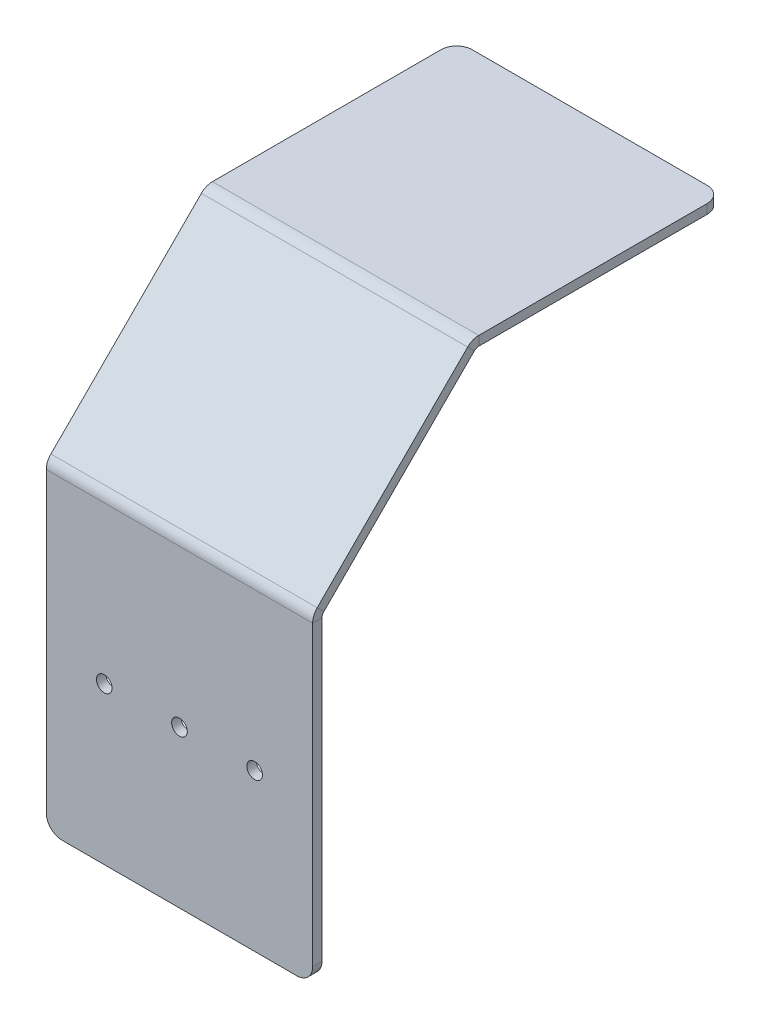
SolidWorks part; units mm, degrees
note: The reader was unsure of these and kept them because the rebuilt part matched: flange length of "Brida de arista1", "Brida de arista2".
ref_plane "Alzado" through (0, 0, 0) normal (0, 0, 1) x (1, 0, 0)
ref_plane "Planta" through (0, 0, 0) normal (0, 1, 0) x (1, 0, 0)
ref_plane "Vista lateral" through (0, 0, 0) normal (1, 0, 0) x (0, 0, -1)
sketch "Croquis1" plane through (0, 0, 0) normal (0, 0, 1) x (1, 0, 0)
  line L1 (-42.5, 50) -> (42.5, 50)
  line L2 (-42.5, 50) -> (-42.5, -50)
  line L3 (-42.5, -50) -> (42.5, -50)
  line L4 (42.5, 50) -> (42.5, -50)
  line L5 (-42.5, 50) -> (42.5, -50) construction
  line L6 (-42.5, -50) -> (42.5, 50) construction
  point P0 (0, 0)
base flange "Brida base3" sketch "Croquis1" thickness 3 reverse thickness direction no parameters "D1"=2
edge flange "Brida de arista1" sketch "Croquis18" flange angle 135 flange length 70 flange position bend outside bend radius 2 thickness 3 parameters "D6"=10
sketch "Croquis18" plane through (0, 50, -3) normal (0, -0.7071, -0.7071) x (-1, 0, 0)
  line L2 (-42.5, 0) -> (-42.5, 68.7574)
  line L3 (-42.5, 68.7574) -> (42.5, 68.7574)
  line L4 (42.5, 68.7574) -> (42.5, 0)
  line L5 (42.5, 0) -> (-42.5, 0) construction
  line L6 (42.5, 0) -> (-42.5, 0)
bend "Pliegue de arista1" bend radius 2 bend angle 45 parameters "D5"=1
sketch "Croquis21" plane through (0, 0, 0) normal (0, 0, 1) x (1, 0, 0)
  circle A0 centre (0, 0) radius 2.5
  circle A1 centre (24, 0) radius 2.5
  circle A2 centre (-24, 0) radius 2.5
extrude "Cortar-Extruir3" cut sketch "Croquis21" against normal blind 35
fillet "Redondeo3" radius 5 1 edges at (42.5, -50, -1.5)
fillet "Redondeo4" radius 5 1 edges at (-42.5, -50, -1.5)
edge flange "Brida de arista2" sketch "Croquis24" flange angle 135 flange length 80 flange position bend outside bend radius 2 thickness 3 parameters "D6"=10
sketch "Croquis24" plane through (0, 99.4472, -51.6188) normal (0, -1, 0) x (-1, 0, 0)
  line L2 (-42.5, 0) -> (-42.5, 78.7574)
  line L3 (-42.5, 78.7574) -> (42.5, 78.7574)
  line L4 (42.5, 78.7574) -> (42.5, 0)
  line L5 (42.5, 0) -> (-42.5, 0) construction
  line L6 (42.5, 0) -> (-42.5, 0)
bend "Pliegue de arista2" bend radius 2 bend angle 45 parameters "D5"=2
fillet "Redondeo5" radius 5 2 edges at (42.5, 101.533, -130.9619) (-42.5, 101.533, -130.9619)
sketch "Líneas de pliegue5" [suppressed] plane through (0, 0, 0) normal (0, 1, 0) x (1, 0, 0)
sketch "Cuadro delimitador5" [suppressed] plane through (0, 0, 0) normal (0, 1, 0) x (1, 0, 0)
sheet metal parameters "Chapa metálica3" thickness 3 parameters "D1"=2
flat pattern "Chapa desplegada3" [suppressed]
sketch "Líneas de pliegue6" plane through (0, 0, 0) normal (0, 1, 0) x (1, 0, 0)
sketch3d "Cuadro delimitador6" [suppressed]
  line L0 (-42.5, 50, 0) -> (-42.5, -50, 0) construction
  line L1 (42.5, 50, 0) -> (42.5, -50, 0) construction
  line L2 (-42.5, 50, 0) -> (42.5, 50, 0) construction
  line L3 (-42.5, -50, 0) -> (42.5, -50, 0) construction
sheet metal parameters "Chapa metálica4" thickness 3 parameters "D1"=2
flat pattern "Chapa desplegada3" [suppressed]
sketch "Líneas de pliegue6" plane through (0, 0, 0) normal (0, 0, 1) x (1, 0, 0)
  line L0 (42.5, 52.2907) -> (-42.5, 52.2907) construction
  line L1 (42.5, 52.2907) -> (-42.5, 52.2907) construction
sketch3d "Cuadro delimitador6" [suppressed]
  line L0 (42.5, 135.7449, 0) -> (42.5, -50, 0) construction
  line L1 (-42.5, 135.7449, 0) -> (-42.5, -50, 0) construction
  line L2 (42.5, 135.7449, 0) -> (-42.5, 135.7449, 0) construction
  line L3 (42.5, -50, 0) -> (-42.5, -50, 0) construction
bend of the flat pattern "Aplanar-<Pliegue de arista1>1"
sketch "Croquis19-1" [suppressed] plane through (0, 36.8109, 0) normal (0, 0, 1) x (1, 0, 0)
  circle A2 centre (0, 89.3523) radius 2.5
  circle A3 centre (0, 27.3523) radius 2.5
sheet metal parameters "Chapa metálica7" thickness 3 parameters "D1"=2
flat pattern "Chapa desplegada3" [suppressed]
sketch "Líneas de pliegue6" plane through (0, 0, 0) normal (0, 0, 1) x (1, 0, 0)
  line L0 (42.5, 51.3744) -> (-42.5, 51.3744) construction
  line L1 (42.5, 51.3744) -> (-42.5, 51.3744) construction
sketch3d "Cuadro delimitador6" [suppressed]
  line L0 (42.5, -50, 0) -> (42.5, 135.6778, 0) construction
  line L1 (-42.5, -50, 0) -> (-42.5, 135.6778, 0) construction
  line L2 (42.5, -50, 0) -> (-42.5, -50, 0) construction
  line L3 (42.5, 135.6778, 0) -> (-42.5, 135.6778, 0) construction
bend of the flat pattern "Aplanar-<Pliegue de arista1>1"
sketch "Croquis19-1" [suppressed] plane through (0, 13.858, 0) normal (0, 0, 1) x (1, 0, 0)
  circle A4 centre (-31, 58.3523) radius 2.5
  circle A5 centre (31, 58.3523) radius 2.5
  dimension "D1" = 5
  dimension "D2" = 5
sheet metal parameters "Chapa metálica8" thickness 3 parameters "D1"=2
flat pattern "Chapa desplegada3"
sketch "Líneas de pliegue6" plane through (0, 0, 0) normal (0, 0, 1) x (1, 0, 0)
  line L0 (42.5, 51.3744) -> (-42.5, 51.3744) construction
  line L1 (42.5, 51.3744) -> (-42.5, 51.3744) construction
  line L2 (42.5, 122.0523) -> (-42.5, 122.0523) construction
  line L3 (42.5, 122.0523) -> (-42.5, 122.0523) construction
sketch3d "Cuadro delimitador6" [suppressed]
  line L0 (42.5, -50, 0) -> (42.5, 201.3557, 0) construction
  line L1 (-42.5, -50, 0) -> (-42.5, 201.3557, 0) construction
  line L2 (42.5, -50, 0) -> (-42.5, -50, 0) construction
  line L3 (42.5, 201.3557, 0) -> (-42.5, 201.3557, 0) construction
bend of the flat pattern "Aplanar-<Pliegue de arista1>1"
bend of the flat pattern "Aplanar-<Pliegue de arista2>1"
equation "\"°90°\"=180"
